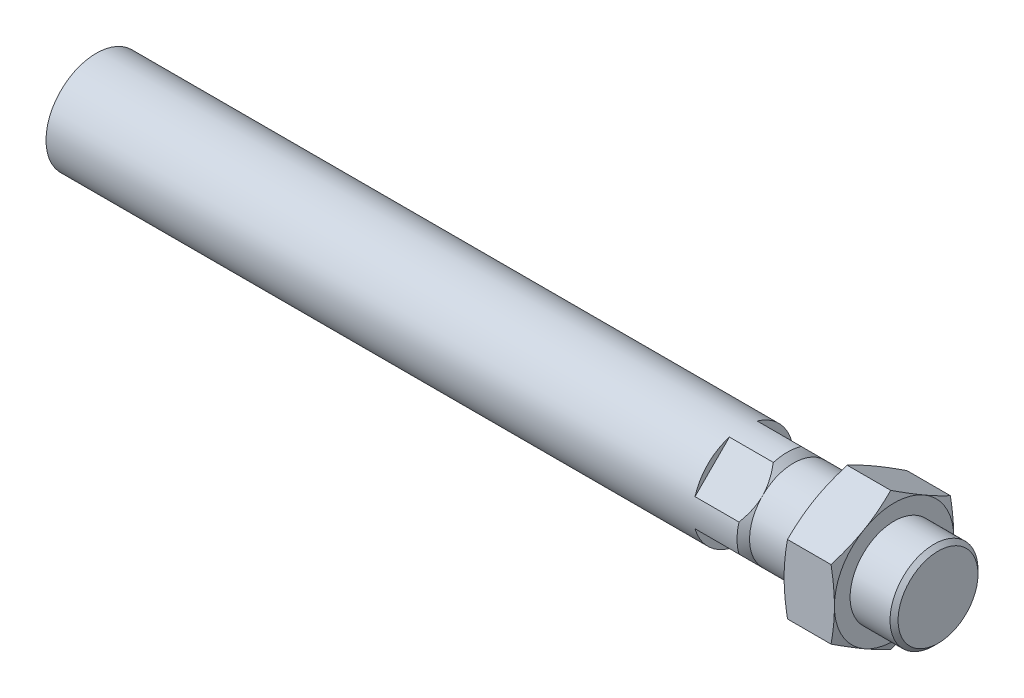
SolidWorks part; units mm, degrees
ref_plane "前视基准面" through (0, 0, 0) normal (0, 0, 1) x (1, 0, 0)
ref_plane "上视基准面" through (0, 0, 0) normal (0, 1, 0) x (1, 0, 0)
ref_plane "右视基准面" through (0, 0, 0) normal (1, 0, 0) x (0, 0, -1)
sketch "草图1" plane through (0, 0, 0) normal (0, 0, 1) x (1, 0, 0)
  line L0 (0, 0) -> (-32, 0) construction
  line L1 (0, 0) -> (0, 10) construction
  point P3 (-7, 0)
  point P4 (-15, 0)
  point P5 (-23, 0)
  point P6 (-134, 0)
  dimension "D1" = 32
  dimension "D2" = 8
  dimension "D3" = 23
  dimension "D4" = 7
  dimension "D5" = 134
  dimension "行程" = 10
sketch "草图2" plane through (0, 0, 0) normal (1, 0, 0) x (0, 0, -1)
  line L0 (0, 0) -> (0, 10) construction
  line L1 (0, 10.9697) -> (-9.5, 5.4848)
  line L2 (-9.5, 5.4848) -> (-9.5, -5.4848)
  line L3 (-9.5, -5.4848) -> (0, -10.9697)
  line L4 (0, -10.9697) -> (9.5, -5.4848)
  line L5 (9.5, -5.4848) -> (9.5, 5.4848)
  line L6 (9.5, 5.4848) -> (0, 10.9697)
  circle A0 centre (0, 0) radius 9.5 construction
  dimension "D1" = 19
extrude "凸台-拉伸1" add sketch "草图2" against normal up to vertex (15 mm away) from vertex up to point (-15, 0, 0) starting at point (-7, 0, 0)
sketch "草图3" plane through (-7, 0, 0) normal (1, 0, 0) x (0, 0, -1)
  circle A0 centre (0, 0) radius 7
  dimension "D1" = 14
extrude "凸台-拉伸2" add sketch "草图3" against normal up to vertex (16 mm away) from vertex up to point (-23, 0, 0) starting at point (0, 0, 0)
cosmetic thread "装饰螺纹线1" parameters "D2"=11.9
cosmetic thread "装饰螺纹线2" parameters "D2"=11.9
sketch "草图4" plane through (-23, 0, 0) normal (-1, 0, 0) x (0, 0, 1)
  circle A0 centre (0, 0) radius 8
  dimension "D1" = 16
extrude "凸台-拉伸3" add sketch "草图4" along normal up to vertex (111 mm away) up to point (-134, 0, 0)
chamfer "倒角1" distance 1 angle 45 1 edges at (-23, 0, 8)
chamfer "倒角2" distance 0.64 angle 45 1 edges at (0, 0, -7)
sketch "草图5" plane through (0, 0, 0) normal (0, 1, 0) x (1, 0, 0)
  line L0 (-7, 9.5) -> (-7, 30.4899)
  line L1 (-7, 9.5) -> (-11, 20.4899)
  line L2 (-11, 9.5) -> (-11, 0) construction
  line L3 (-15, 9.5) -> (-7, 9.5) construction
  line L4 (0, 0) -> (-32, 0) construction
  line L5 (-15, 9.5) -> (-11, 20.4899)
  line L6 (-15, 9.5) -> (-15, 30.4899)
  line L7 (-15, 30.4899) -> (-7, 30.4899)
  dimension "D1" = 20
  dimension "D2" = 10
revolve "切除-旋转1" cut sketch "草图5" angle 360 about L0
sketch "草图6" plane through (0, 0, 0) normal (1, 0, 0) x (0, 0, -1)
  line L0 (0, 0) -> (0, 10) construction
  line L1 (0, 9.8995) -> (-9.8995, 0)
  line L2 (-9.8995, 0) -> (0, -9.8995)
  line L3 (0, -9.8995) -> (9.8995, 0)
  line L4 (9.8995, 0) -> (0, 9.8995)
  circle A0 centre (0, 0) radius 7 construction
  dimension "D1" = 14
extrude "切除-拉伸2" cut sketch "草图6" against normal blind 8 from vertex flip side to cut starting at point (-23, 0, 0)
equation "\"D5@草图1\" = 52+95+\"行程@草图1\"-23"
equation "\"D1@倒角2\" = \"D1@草图3\"/100+0.5"
